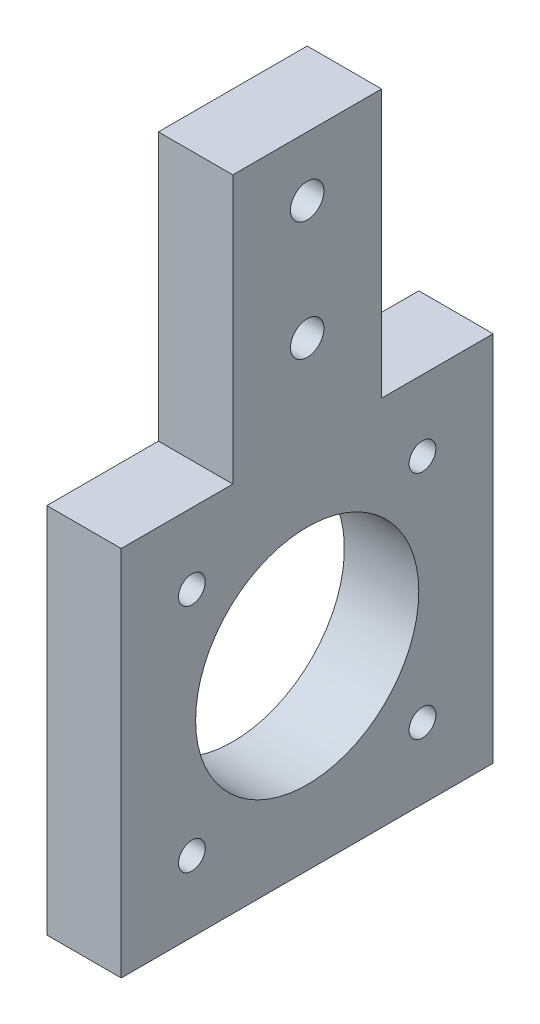
SolidWorks part; units mm, degrees
ref_plane "Front Plane" through (0, 0, 0) normal (0, 0, 1) x (1, 0, 0)
ref_plane "Top Plane" through (0, 0, 0) normal (0, 1, 0) x (1, 0, 0)
ref_plane "Right Plane" through (0, 0, 0) normal (1, 0, 0) x (0, 0, -1)
sketch "Sketch1" plane through (0, 0, 0) normal (0, 1, 0) x (1, 0, 0)
  line L1 (-10, -10) -> (10, -10)
  line L2 (-10, -10) -> (-10, 10)
  line L3 (-10, 10) -> (10, 10)
  line L4 (10, -10) -> (10, 10)
  line L5 (-10, -10) -> (10, 10) construction
  line L6 (-10, 10) -> (10, -10) construction
  line L7 (-14, 14) -> (14, 14)
  line L8 (-14, 14) -> (-14, -14)
  line L9 (-14, -14) -> (14, -14)
  line L10 (14, 14) -> (14, -14)
  line L11 (-14, 14) -> (14, -14) construction
  line L12 (-14, -14) -> (14, 14) construction
  point P0 (0, 0)
  point P5 (0, 0)
  dimension "D1" = 20
  dimension "D2" = 28
extrude "Boss-Extrude1" add sketch "Sketch1" along normal blind 40
sketch "Sketch2" plane through (-14, 0, 0) normal (-1, 0, 0) x (0, 0, 1)
  line L0 (0, 40) -> (0, 32)
  line L1 (0, 0) -> (0, 16)
  line L4 (-14, 0) -> (14, 0)
  line L5 (14, 0) -> (14, 40)
  line L6 (14, 40) -> (-14, 40)
  line L7 (-14, 40) -> (-14, 0)
  line L8 (-14, 0) -> (14, 0)
  line L9 (14, 0) -> (14, 40)
  line L10 (14, 40) -> (-14, 40)
  line L11 (-14, 40) -> (-14, 0)
  circle A0 centre (0, 32) radius 2.25
  circle A1 centre (0, 16) radius 2.25
  dimension "D3" = 4.5
  dimension "D5" = 4.5
  dimension "D2" = 8
  dimension "D4" = 16
  dimension "D1" = 0
extrude "Cut-Extrude1" cut sketch "Sketch2" against normal blind 30 contours A1 | A0 region at (-14, 33.546, 1.546) region at (-14, 17.546, -1.546)
sketch "Sketch5" plane through (-14, 0, 0) normal (-1, 0, 0) x (0, 0, 1)
  line L0 (0, 0) -> (0, -21)
  line L1 (0, -21) -> (-15.4998, -5.5002) construction
  line L2 (-25, -46) -> (25, -46)
  line L3 (-25, -46) -> (-25, 4)
  line L4 (-14, 0) -> (14, 0)
  line L5 (14, 0) -> (14, 40)
  line L6 (14, 40) -> (-14, 40)
  line L7 (-14, 40) -> (-14, 0)
  line L8 (-14, 0) -> (14, 0)
  line L9 (14, 0) -> (14, 40)
  line L10 (14, 40) -> (-14, 40)
  line L11 (-14, 40) -> (-14, 0)
  line L12 (-25, 4) -> (25, 4)
  line L13 (25, -46) -> (25, 4)
  line L14 (-25, -46) -> (25, 4) construction
  line L15 (-25, 4) -> (25, -46) construction
  line L16 (-15.4998, -5.5002) -> (15.4998, -5.5002) construction
  line L17 (15.4998, -5.5002) -> (15.4998, -36.4998) construction
  line L18 (15.4998, -36.4998) -> (-15.4998, -36.4998) construction
  circle A0 centre (-15.4998, -5.5002) radius 1.8
  circle A1 centre (15.4998, -5.5002) radius 1.8
  circle A2 centre (15.4998, -36.4998) radius 1.8
  circle A3 centre (-15.4998, -36.4998) radius 1.8
  circle A4 centre (0, -21) radius 15
  line M7 (-14, 0) -> (14, 0)
  line M8 (14, 0) -> (14, 40)
  dimension "D5" = 3.6
  dimension "D6" = 30
  dimension "D2" = 21
  dimension "D3" = 50
  dimension "D4" = 21.92
  dimension "D1" = 0
extrude "Boss-Extrude2" add sketch "Sketch5" against normal up to surface (4 mm away) contours A4 L11 L12 L3 L2 L13 A3 A2 A1 A0 M7 M8 region at (-14, -0.7071, 7) up to face at (-10, 16, -2.25)
sketch "Sketch6" plane through (0, 0, 0) normal (0, -1, 0) x (1, 0, 0)
  line L0 (-10, 14) -> (14, 14) construction
  line L1 (-10, 14) -> (14, 14)
  line L2 (-10, 14) -> (-10, -14)
  line L3 (-10, -14) -> (14, -14)
  line L4 (14, 14) -> (14, -14)
  dimension "D1" = 24
extrude "Cut-Extrude2" cut sketch "Sketch6" against normal blind 40
sketch "Sketch7" plane through (-14, 0, 0) normal (-1, 0, 0) x (0, 0, 1)
  line L0 (-10, 0) -> (10, 0)
  line L1 (-10, 0) -> (-10, 40)
  line L2 (-14, 40) -> (14, 40) construction
  line L3 (-10, 40) -> (10, 40)
  line L4 (10, 40) -> (10, 0)
  line L6 (-14, 40) -> (-10, 40)
  line L7 (-14, 40) -> (-14, 4)
  line L8 (-14, 4) -> (-10, 4)
  line L9 (-10, 40) -> (-10, 4)
  line L10 (14, 40) -> (10, 40)
  line L11 (14, 40) -> (14, 4)
  line L12 (14, 4) -> (10, 4)
  line L13 (10, 40) -> (10, 4)
  point P4 (0, 0)
  line M7 (-14, 40) -> (-14, 4)
  line M13 (14, 4) -> (14, 40)
  line M14 (14, 40) -> (-14, 40)
  dimension "D1" = 20
  dimension "D2" = 36
  dimension "D3" = 4
  dimension "D4" = 36
  dimension "D5" = 4
extrude "Cut-Extrude3" cut sketch "Sketch7" against normal blind 4 contours L8 L1 M7 M14 | L12 L4 M13 M14 region at (-14, 22, -12) region at (-14, 22, 12)
sketch "Sketch8" plane through (-14, 0, 0) normal (-1, 0, 0) x (0, 0, 1)
  line L8 (10, 40) -> (-10, 40)
  line L9 (-10, 40) -> (-10, 4)
  line L10 (-10, 4) -> (-25, 4)
  line L11 (-25, 4) -> (-25, -46)
  line L12 (-25, -46) -> (25, -46)
  line L13 (25, -46) -> (25, 4)
  line L14 (25, 4) -> (10, 4)
  line L15 (10, 4) -> (10, 40)
  line L16 (10, 40) -> (-10, 40)
  line L17 (-10, 40) -> (-10, 4)
  line L18 (-10, 4) -> (-25, 4)
  line L19 (-25, 4) -> (-25, -46)
  line L20 (-25, -46) -> (25, -46)
  line L21 (25, -46) -> (25, 4)
  line L22 (25, 4) -> (10, 4)
  line L23 (10, 4) -> (10, 40)
  circle A0 centre (15.4998, -5.5002) radius 1.8 construction
  circle A1 centre (15.4998, -36.4998) radius 1.8 construction
  circle A2 centre (-15.4998, -36.4998) radius 1.8 construction
  circle A3 centre (0, -21) radius 15 construction
  circle A4 centre (-15.4998, -5.5002) radius 1.8 construction
  circle A5 centre (0, 16) radius 2.25 construction
  circle A6 centre (0, 32) radius 2.25 construction
  circle A7 centre (15.4998, -5.5002) radius 1.8
  circle A8 centre (15.4998, -36.4998) radius 1.8
  circle A9 centre (-15.4998, -36.4998) radius 1.8
  circle A10 centre (0, -21) radius 15
  circle A11 centre (-15.4998, -5.5002) radius 1.8
  circle A12 centre (0, 16) radius 2.25
  circle A13 centre (0, 32) radius 2.25
  dimension "D1" = 0
extrude "Boss-Extrude3" add sketch "Sketch8" along normal blind 6
